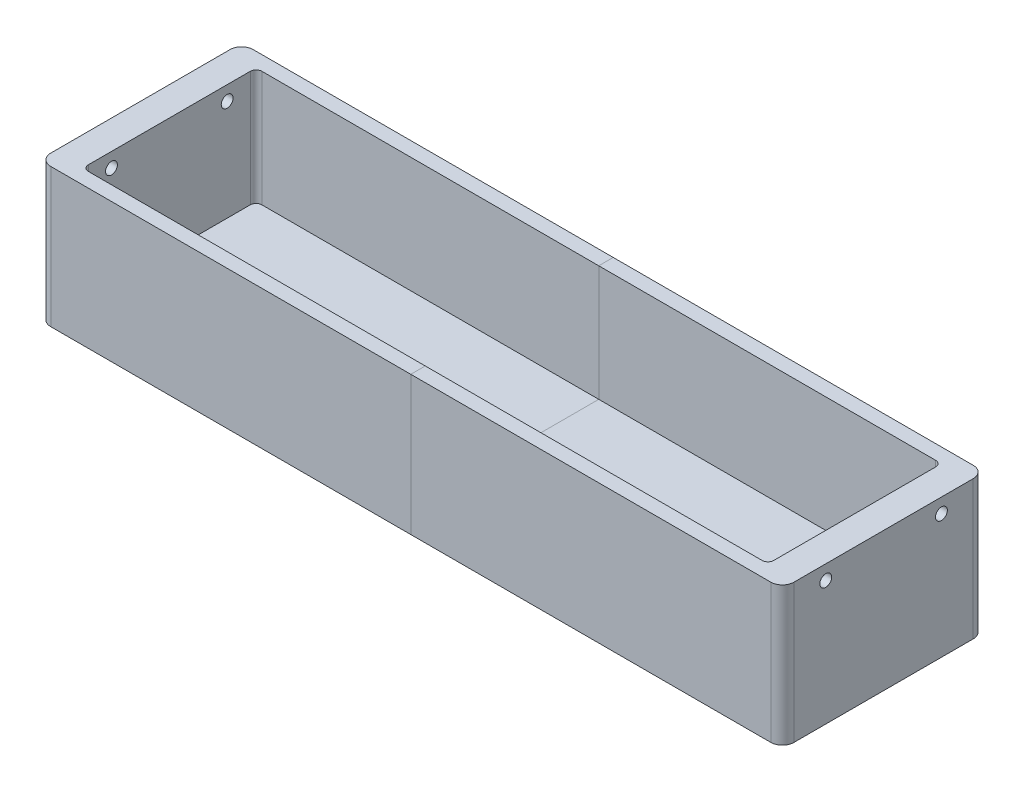
SolidWorks part; units mm, degrees
ref_plane "Front Plane" through (0, 0, 0) normal (0, 0, 1) x (1, 0, 0)
ref_plane "Top Plane" through (0, 0, 0) normal (0, 1, 0) x (1, 0, 0)
ref_plane "Right Plane" through (0, 0, 0) normal (1, 0, 0) x (0, 0, -1)
sketch "Sketch1" plane through (0, 0, 0) normal (0, 1, 0) x (1, 0, 0)
  line L1 (-131.445, -31.75) -> (131.445, -31.75) construction
  line L2 (-131.445, -31.75) -> (-131.445, 31.75) construction
  line L3 (-131.445, 31.75) -> (131.445, 31.75) construction
  line L4 (131.445, -31.75) -> (131.445, 31.75) construction
  line L5 (0, 31.75) -> (0, -31.75) construction
  line L6 (-131.445, 0) -> (131.445, 0) construction
  line L11 (-163.195, -44.45) -> (163.195, -44.45)
  line L12 (-163.195, -44.45) -> (-163.195, 44.45)
  line L13 (-163.195, 44.45) -> (163.195, 44.45)
  line L14 (163.195, -44.45) -> (163.195, 44.45)
  line L15 (0, 44.45) -> (0, -44.45) construction
  line L16 (-163.195, 0) -> (163.195, 0) construction
  line L17 (-150.495, -38.1) -> (150.495, -38.1)
  line L18 (-150.495, -38.1) -> (-150.495, 38.1)
  line L23 (0, 38.1) -> (0, -38.1) construction
  line L24 (-150.495, 0) -> (150.495, 0) construction
  line L25 (-150.495, 38.1) -> (150.495, 38.1)
  line L26 (150.495, -38.1) -> (150.495, 38.1)
  line L27 (0, 38.1) -> (0, -38.1) construction
  line L28 (-150.495, 0) -> (150.495, 0) construction
  point P0 (0, 0)
  point P4 (0, 0)
  point P8 (0, 0)
  point P13 (0, 0)
  dimension "D1" = 131.445
  dimension "D2" = 63.5
  dimension "D4" = 6.35
  dimension "D5" = 12.7
  dimension "D3" = 19.05
  dimension "D6" = 6.35
extrude "Boss-Extrude1" add sketch "Sketch1" along normal blind 50.8
sketch "Sketch2" plane through (0, 0, 0) normal (0, -1, 0) x (1, 0, 0)
  line L4 (163.195, -44.45) -> (163.195, 44.45)
  line L5 (163.195, 44.45) -> (-163.195, 44.45)
  line L6 (-163.195, 44.45) -> (-163.195, -44.45)
  line L7 (-163.195, -44.45) -> (163.195, -44.45)
  line L8 (163.195, -44.45) -> (163.195, 44.45)
  line L9 (163.195, 44.45) -> (-163.195, 44.45)
  line L10 (-163.195, 44.45) -> (-163.195, -44.45)
  line L11 (-163.195, -44.45) -> (163.195, -44.45)
  dimension "D1" = 0
extrude "Boss-Extrude2" add sketch "Sketch2" along normal blind 10.16
sketch "Sketch3" plane through (0, -10.16, 0) normal (0, -1, 0) x (1, 0, 0)
  line L0 (27.94, 0) -> (-27.94, 0) construction
  circle A0 centre (-106, 7.5) radius 3.1
  circle A1 centre (-106, -7.5) radius 3.1
  dimension "D2" = 6.2
  dimension "D1" = 106
  dimension "D3" = 7.5
extrude "Cut-Extrude1" cut sketch "Sketch3" against normal through all
sketch "Sketch4" plane through (163.195, 0, 0) normal (1, 0, 0) x (0, 0, -1)
  line L1 (0, 27.94) -> (0, -27.94) construction
  line L2 (-38.1, 0) -> (38.1, 0) construction
  circle A0 centre (25.4, 44.45) radius 2.6
  circle A1 centre (-25.4, 44.45) radius 2.6
  dimension "D2" = 5.2
  dimension "D1" = 44.45
  dimension "D3" = 25.4
extrude "Cut-Extrude3" cut sketch "Sketch4" against normal up to surface (12.7 mm away) up to face at (150.495, 25.4, 0)
mirror "Mirror2" about plane through (0, 0, 0) normal (1, 0, 0) of "Cut-Extrude3"
fillet "Fillet1" radius 5.08 4 edges at (163.195, 20.32, -44.45) (163.195, 20.32, 44.45) (-163.195, 20.32, -44.45) (-163.195, 20.32, 44.45)
fillet "Fillet2" radius 2.54 4 edges at (150.495, 25.4, 38.1) (150.495, 25.4, -38.1) (-150.495, 25.4, 38.1) (-150.495, 25.4, -38.1)
split "Split1" trim tools "Right Plane" bodies to split 107 resulting bodies 108 109
